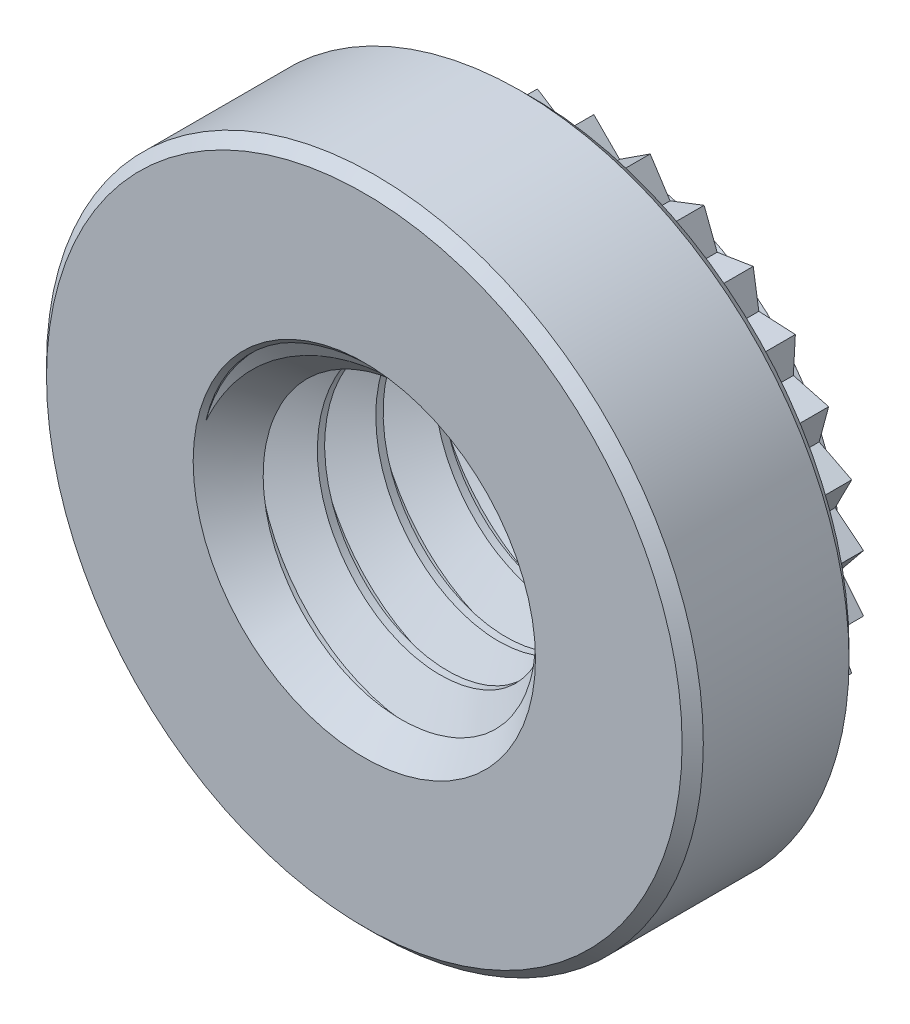
SolidWorks part; units mm, degrees
ref_plane "Front Plane" through (0, 0, 0) normal (0, 0, 1) x (1, 0, 0)
ref_plane "Top Plane" through (0, 0, 0) normal (0, 1, 0) x (1, 0, 0)
ref_plane "Right Plane" through (0, 0, 0) normal (1, 0, 0) x (0, 0, -1)
sketch "Sketch1" plane through (0, 0, 0) normal (0, 0, 1) x (1, 0, 0)
  circle A0 centre (0, 0) radius 3.935
  dimension "A" = 7.87
extrude "Extrude1" add sketch "Sketch1" against normal blind 2
sketch "Sketch15" plane through (0, 0, -2) normal (0, 0, -1) x (-1, 0, 0)
  circle A0 centre (0, 0) radius 2.7
  dimension "hole dia" = 5.4
sketch "Sketch2" plane through (0, 0, -2) normal (0, 0, -1) x (-1, 0, 0)
  circle A0 centre (0, 0) radius 2.7125
  dimension "D1" = 5.425
extrude "Extrude2" add sketch "Sketch2" along normal blind 1
sketch "Sketch3" plane through (0, 0, -3) normal (0, 0, -1) x (-1, 0, 0)
  line L0 (0, 2.522) -> (0, 3.935)
  circle A1 centre (0, 0) radius 3.935 construction
  circle A2 centre (0, 0) radius 2.522
  circle A3 centre (0, 0) radius 2.522 construction
  dimension "D1" = 0.1905
sketch "Sketch5" plane through (0, 0, -3) normal (0, 0, -1) x (-1, 0, 0)
  circle A0 centre (0, 0) radius 3.935 construction
  circle A3 centre (0, 0) radius 2.69
  dimension "C" = 5.38
extrude "Cut-Extrude1" cut sketch "Sketch5" against normal blind 0.25 draft 20 flip side to cut draft outward yes
chamfer "Chamfer2" distance 0.127 angle 45 2 edges at (3.935, 0, 0) (3.935, 0, -2)
sketch "Sketch7" plane through (0, 0, 0) normal (0, 0, 1) x (1, 0, 0)
  circle A0 centre (0, 0) radius 2
  dimension "Thread Od" = 4
extrude "Cut-Extrude3" cut sketch "Sketch7" against normal through all
sketch "Sketch8" plane through (0, 0, -3) normal (0, 0, -1) x (-1, 0, 0)
  circle A0 centre (0, 0) radius 2 construction
  circle A1 centre (0, 0) radius 2
curve "Helix/Spiral1" pitch 0.7 height 5 radius 2 centre (0, 0, -3) axis (0, 0, 1) start towards (0, 1, 0) parameters "pitch"=0.7
sketch "Sketch9" plane through (0, 0, 0) normal (1, 0, 0) x (0, 0, -1)
  line L0 (3.6125, 2) -> (3.35, 1.5453)
  line L1 (3.35, 1.5453) -> (3.2625, 1.5453)
  line L2 (3.2625, 1.5453) -> (3, 2)
  line L3 (3.6125, 2) -> (3, 2)
  line L4 (3.3062, 2) -> (3.3062, 1.5453) construction
  line L5 (3.4813, 1.7727) -> (3.1313, 1.7727) construction
  line L6 (3, -2) -> (3, 2) construction
  dimension "D1" = 60
  dimension "D2" = 0.0875
  dimension "D3" = 0.35
sweep "Sweep1" add profiles "Sketch9" path "Helix/Spiral1"
sketch "Sketch10" plane through (0, 0, 0) normal (0, 0, 1) x (1, 0, 0)
  circle A0 centre (0, 0) radius 3.935 construction
  circle A1 centre (0, 0) radius 3.935
extrude "Cut-Extrude4" cut sketch "Sketch10" along normal through all
sketch "Sketch11" plane through (0, 0, -3) normal (0, 0, -1) x (-1, 0, 0)
  circle A1 centre (0, 0) radius 2.69 construction
  circle A2 centre (0, 0) radius 2.69
extrude "Cut-Extrude5" cut sketch "Sketch11" along normal through all
sketch "Sketch13" plane through (0, 0, 0) normal (0, 0, 1) x (1, 0, 0)
  circle A2 centre (0, 0) radius 2.0508
  circle A3 centre (0, 0) radius 2.0508
  dimension "D1" = 0.0508
extrude "Cut-Extrude6" cut sketch "Sketch13" against normal through all draft 45
sketch "Sketch14" plane through (0, 0, -3) normal (0, 0, -1) x (-1, 0, 0)
  circle A2 centre (0, 0) radius 2.0635
  circle A3 centre (0, 0) radius 2.0635
  dimension "D1" = 0.0635
extrude "Cut-Extrude7" cut sketch "Sketch14" against normal through all draft 45
sketch "Sketch16" plane through (0, 0, -2.75) normal (0, 0, -1) x (-1, 0, 0)
  line L0 (0, 2.69) -> (0, 3.808) construction
  line L1 (0, 3.249) -> (-0.6028, 2.6447)
  line L2 (0, 3.249) -> (0.6028, 2.6447)
  circle A0 centre (0, 0) radius 2.599 construction
  circle A1 centre (0, 0) radius 2.69 construction
  circle A2 centre (0, 0) radius 3.808 construction
  circle A3 centre (0, 0) radius 2.7125 construction
  arc A4 (-0.6028, 2.6447) -> (0.6028, 2.6447) centre (0, 0) cw
  circle A5 centre (0, 0) radius 2.7125 construction
  point P2 (0, 3.249)
  dimension "D2" = 1.2056
extrude "Boss-Extrude1" add sketch "Sketch16" against normal up to surface (0.75 mm away) up to face at (3.808, 0, -2)
pattern_circular "CirPattern4" count 30 over 360 about axis through (0, 0, -3) along (0, 0, -1) of "Boss-Extrude1"
equation "\"D3@Helix/Spiral1\"=\"B@Extrude1\"+\"panel min.@Extrude2\"+2"
equation "\"D2@Sketch9\" = \"pitch@Helix/Spiral1\"*.125"
equation "\"D3@Sketch9\" = \"pitch@Helix/Spiral1\"*.50"
equation "\"D1@Sketch2\" = \"hole dia@Sketch15\"+.025"
equation "\"D1@Cut-Extrude1\" = \"panel min.@Extrude2\"*.25"
equation "\"D2@Sketch16\"=\"D1@Sketch2\"/4.5"
equation "\"D1@CirPattern4\"=360/12"
